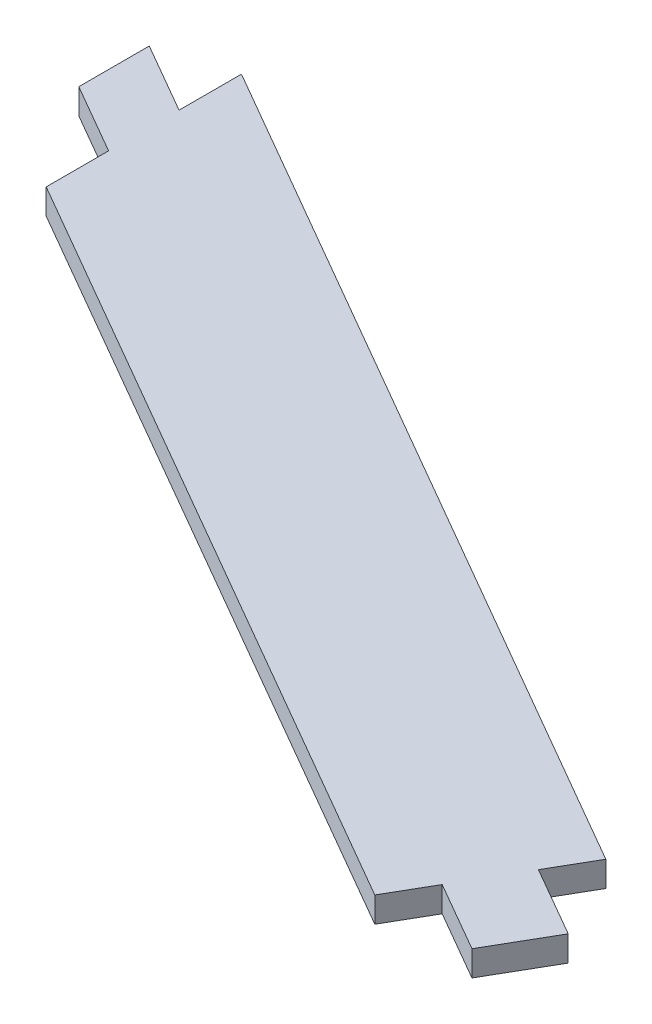
SolidWorks part; units mm, degrees
ref_plane "Front Plane" through (0, 0, 0) normal (0, 0, 1) x (1, 0, 0)
ref_plane "Top Plane" through (0, 0, 0) normal (0, 1, 0) x (1, 0, 0)
ref_plane "Right Plane" through (0, 0, 0) normal (1, 0, 0) x (0, 0, -1)
sketch "Sketch1" plane through (0, 0, 0) normal (0, 1, 0) x (1, 0, 0)
  line L0 (-363.1089, 480) -> (-363.1089, -480)
  line L1 (-363.1089, -480) -> (-303.1089, -480)
  line L2 (-303.1089, -480) -> (-303.1089, -400)
  line L3 (-303.1089, -400) -> (303.1089, -50)
  line L4 (303.1089, -50) -> (1036.8911, -50)
  line L5 (1036.8911, -50) -> (1036.8911, 50) construction
  line L6 (1036.8911, 50) -> (303.1089, 50)
  line L7 (303.1089, 50) -> (-303.1089, 400)
  line L8 (-303.1089, 400) -> (-303.1089, 480)
  line L9 (-303.1089, 480) -> (-363.1089, 480)
  line L10 (-363.1089, 0) -> (1036.8911, 0) construction
  line L11 (0, 225) -> (0, -225) construction
  line L14 (1036.8911, 50) -> (1066.8911, 50)
  line L15 (1036.8911, 50) -> (1036.8911, -50) construction
  line L16 (1036.8911, -50) -> (1066.8911, -50)
  line L17 (1066.8911, 50) -> (1066.8911, -50)
  dimension "D1" = 960
  dimension "D2" = 60
  dimension "D3" = 100
  dimension "D4" = 1400
  dimension "D5" = 150
  dimension "D6" = 80
  dimension "D7" = 30
extrude "Boss-Extrude1" add sketch "Sketch1" along normal blind 9
sketch "Sketch2" plane through (0, 9, 0) normal (0, 1, 0) x (1, 0, 0)
  line L1 (-363.1089, 480) -> (-303.1089, 480)
  line L2 (-363.1089, 480) -> (-363.1089, 400)
  line L3 (-363.1089, 400) -> (-303.1089, 400)
  line L4 (-303.1089, 480) -> (-303.1089, 400)
  line L5 (-363.1089, -480) -> (-303.1089, -480)
  line L6 (-363.1089, -480) -> (-363.1089, -400)
  line L7 (-363.1089, -400) -> (-303.1089, -400)
  line L8 (-303.1089, -480) -> (-303.1089, -400)
extrude "Boss-Extrude2" add sketch "Sketch2" along normal blind 500
sketch "Sketch3" plane through (0, 0, 0) normal (0, 0, 1) x (1, 0, 0)
  line L0 (-333.1089, 509) -> (-333.1089, 254.2) construction
  line L1 (-363.1089, 509) -> (-303.1089, 509) construction
  line L2 (-333.1089, 254.2) -> (-333.1089, 25) construction
  line L3 (-333.1089, 25) -> (-333.1089, 0) construction
  line L4 (-363.1089, 0) -> (-303.1089, 0) construction
  line L6 (-363.1089, 509) -> (-303.1089, 509)
  line L7 (-363.1089, 509) -> (-363.1089, 9)
  line L8 (-363.1089, 9) -> (-303.1089, 9)
  line L9 (-303.1089, 509) -> (-303.1089, 9)
  circle A0 centre (-333.1089, 254.2) radius 229.2
  circle A1 centre (-333.1089, 254.2) radius 6
  circle A2 centre (-333.1089, 254.2) radius 30
  dimension "D1" = 458.4
  dimension "D3" = 12
  dimension "D2" = 25
extrude "Cut-Extrude1" cut sketch "Sketch3" against normal through all both and the other way through all contours A2 L9 A0 L7 | A0 L9 L6 L7 | A1 region at (-333.1089, 495.8654, 0) region at (-333.1089, 380.1444, 0) region at (-333.1089, 254.2, 0)
sketch "Sketch4" plane through (0, 9, 0) normal (0, 1, 0) x (1, 0, 0)
  line L0 (866.8911, 25) -> (1066.8911, 25)
  line L2 (866.8911, -25) -> (1066.8911, -25)
  line L3 (1066.8911, -25) -> (1066.8911, 25)
  line L4 (866.8911, 0) -> (1066.8911, 0) construction
  line L5 (1066.8911, -50) -> (1066.8911, 50) construction
  circle A0 centre (866.8911, 0) radius 25
  dimension "D1" = 50
  dimension "D2" = 200
extrude "Cut-Extrude2" cut sketch "Sketch4" against normal through all contours L4 A0 L2 | A0 L4 L3 L0 | A0 region at (976.6223, 9, -12.7057) region at (884.0688, 9, -17.1777) region at (976.6223, 9, 12.7057)
sketch "Sketch16" plane through (0, 0, 0) normal (0, 0, 1) x (1, 0, 0)
  line L0 (-359.656, 240.2268) -> (-348.1089, 218.2888)
  line L5 (-348.1089, 218.2888) -> (-348.1089, 24)
  line L7 (-363.1089, 9) -> (-288.1089, 9)
  line L8 (303.1089, 9) -> (-303.1089, 9) construction
  line L9 (-303.1089, 254.2) -> (-303.1089, 24)
  line L10 (-348.1089, 24) -> (-363.1089, 9)
  line L11 (-303.1089, 254.2) -> (-303.1089, 9) construction
  line L12 (-303.1089, 24) -> (-288.1089, 9)
  line L13 (-348.1089, 24) -> (-303.1089, 24) construction
  line L14 (-346.3825, 247.2134) -> (-358.4836, 270.2039)
  line L15 (-319.8353, 261.1866) -> (-331.9364, 284.1771)
  circle A0 centre (-333.1089, 254.2) radius 15
  circle A1 centre (-333.1089, 254.2) radius 30
  arc A2 (-303.1089, 254.2) -> (-363.1089, 254.2) centre (-333.1089, 254.2) ccw construction
  circle A3 centre (-360.6089, 215.2) radius 12.5 construction
  dimension "D1" = 30
  dimension "D4" = 25
  dimension "D2" = 45
  dimension "D3" = 45
extrude "Boss-Extrude8" add sketch "Sketch16" along normal blind 305 and the other way blind 305 contours A1 L0 L5 L10 L7 L12 L9 | A1 L15 A0 L14 region at (-325.4564, 117.1914, 0) region at (-362.2383, 255.3393, 0)
sketch "Sketch17" plane through (0, 0, 0) normal (1, 0, 0) x (0, 0, -1)
  line L1 (230, 309) -> (-230, 309)
  line L2 (230, 309) -> (230, 9)
  line L3 (230, 9) -> (-230, 9)
  line L4 (-230, 309) -> (-230, 9)
  line L5 (0, 0) -> (0, 309) construction
  line L6 (480, 0) -> (-480, 0) construction
  dimension "D1" = 460
  dimension "D2" = 9
  dimension "D3" = 300
extrude "Cut-Extrude9" cut sketch "Sketch17" against normal through all
sketch "Sketch7" plane through (0, 0, 0) normal (1, 0, 0) x (0, 0, -1)
  line L1 (480, 284.2) -> (230, 284.2)
  line L2 (480, 284.2) -> (480, 9)
  line L3 (480, 9) -> (230, 9)
  line L4 (230, 284.2) -> (230, 9)
  line L5 (230, 218.2888) -> (230, 24) construction
  line L6 (471, 146.6) -> (444.5, 146.6) construction
  line L7 (480, 284.2) -> (471, 284.2)
  line L8 (480, 284.2) -> (480, 9)
  line L9 (480, 9) -> (471, 9)
  line L10 (471, 284.2) -> (471, 9)
  line L11 (400, 9) -> (409, 9)
  line L12 (400, 9) -> (400, 284.2)
  line L13 (400, 284.2) -> (409, 284.2)
  line L14 (409, 9) -> (409, 284.2)
  line L15 (444.5, 284.2) -> (435.5, 284.2)
  line L16 (444.5, 284.2) -> (444.5, 9)
  line L17 (444.5, 9) -> (435.5, 9)
  line L18 (435.5, 284.2) -> (435.5, 9)
  line L19 (444.5, 146.6) -> (435.5, 146.6) construction
  line L20 (435.5, 146.6) -> (409, 146.6) construction
  line L22 (0, 274.5241) -> (0, -136.9768) construction
  line L23 (-435.5, 146.6) -> (-409, 146.6) construction
  line L24 (305, 284.2) -> (296, 284.2)
  line L25 (305, 284.2) -> (305, 9)
  line L26 (305, 9) -> (296, 9)
  line L27 (296, 284.2) -> (296, 9)
  line L28 (239, 9) -> (230, 9)
  line L29 (239, 9) -> (239, 284.2)
  line L30 (239, 284.2) -> (230, 284.2)
  line L31 (230, 9) -> (230, 284.2)
  line L32 (-444.5, 146.6) -> (-435.5, 146.6) construction
  line L33 (-471, 146.6) -> (-444.5, 146.6) construction
  line L34 (-230, 9) -> (-230, 284.2)
  line L35 (-239, 284.2) -> (-230, 284.2)
  line L36 (-239, 9) -> (-239, 284.2)
  line L37 (-239, 9) -> (-230, 9)
  line L38 (-296, 284.2) -> (-296, 9)
  line L39 (-305, 9) -> (-296, 9)
  line L40 (-305, 284.2) -> (-305, 9)
  line L41 (-305, 284.2) -> (-296, 284.2)
  line L42 (-435.5, 284.2) -> (-435.5, 9)
  line L43 (-444.5, 9) -> (-435.5, 9)
  line L44 (-444.5, 284.2) -> (-444.5, 9)
  line L45 (-444.5, 284.2) -> (-435.5, 284.2)
  line L46 (-409, 9) -> (-409, 284.2)
  line L47 (-400, 284.2) -> (-409, 284.2)
  line L48 (-400, 9) -> (-400, 284.2)
  line L49 (-400, 9) -> (-409, 9)
  line L50 (-471, 284.2) -> (-471, 9)
  line L51 (-480, 9) -> (-471, 9)
  line L52 (-480, 284.2) -> (-480, 9)
  line L53 (-480, 284.2) -> (-471, 284.2)
  line L54 (-230, 284.2) -> (-230, 9)
  line L55 (-480, 9) -> (-230, 9)
  line L56 (-480, 284.2) -> (-480, 9)
  line L57 (-480, 284.2) -> (-230, 284.2)
  line L58 (305, 218.2888) -> (305, 24) construction
  dimension "D1" = 9
  dimension "D2" = 9
  dimension "D3" = 9
  dimension "D4" = 9
  dimension "D5" = 9
extrude "Cut-Extrude4" cut sketch "Sketch7" against normal through all both and the other way through all contours L1 L16 L3 L10 | L18 L1 L14 L3 | L29 L3 L27 L1 | L57 L38 L55 L36 | L57 L42 L55 L46 | L57 L50 L55 L44 | L1 L18 L3 L16 | L45 L44 L43 L42 region at (0, 146.6, -457.75) region at (0, 146.6, -440) region at (0, 146.6, -422.25) region at (0, 146.6, -267.5) region at (0, 146.6, 267.5) region at (0, 146.6, 422.25) region at (0, 146.6, 440) region at (0, 146.6, 457.75)
sketch "Sketch10" plane through (0, 9, 0) normal (0, 1, 0) x (1, 0, 0)
  line L0 (-363.1089, 221) -> (-113.0718, 221)
  line L2 (-113.0718, 221) -> (269.7114, 0)
  line L3 (269.7114, 0) -> (-113.0718, -221)
  line L4 (-113.0718, -221) -> (-363.1089, -221)
  line L5 (-363.1089, -221) -> (-363.1089, 221)
  line L6 (0, 0) -> (269.7114, 0) construction
  line L7 (-363.1089, 0) -> (0, 0) construction
  line L8 (-113.0718, -221) -> (-113.0718, 221) construction
  line L9 (303.1089, 50) -> (-303.1089, 400) construction
  line L10 (-363.1089, -230) -> (-363.1089, 230) construction
  line L11 (303.1089, 50) -> (337.7499, 30)
  line L12 (337.7499, 30) -> (806.8911, 30)
  line L13 (806.8911, 30) -> (841.5321, 50)
  line L14 (1066.8911, 50) -> (303.1089, 50) construction
  line L15 (841.5321, 50) -> (303.1089, 50)
  line L16 (303.1089, -50) -> (337.7499, -30)
  line L17 (337.7499, -30) -> (806.8911, -30)
  line L18 (806.8911, -30) -> (841.5321, -50)
  line L19 (303.1089, -50) -> (1066.8911, -50) construction
  line L20 (841.5321, -50) -> (303.1089, -50)
  line L21 (337.7499, -30) -> (337.7499, 30) construction
  line L22 (269.7114, 0) -> (337.7499, 0) construction
  line L23 (806.8911, 30) -> (806.8911, -30) construction
  line L24 (-303.1089, -400) -> (303.1089, -50) construction
  line L25 (841.5321, 50) -> (841.5321, -50) construction
  line L27 (-363.1089, 230) -> (-288.1089, 230) construction
  line L28 (-363.1089, -230) -> (-288.1089, -230) construction
  arc A0 (866.8911, 25) -> (866.8911, -25) centre (866.8911, 0) ccw construction
  dimension "D1" = 60
  dimension "D2" = 30
  dimension "D3" = 60
  dimension "D4" = 60
  dimension "D5" = 9
  dimension "D6" = 9
extrude "Cut-Extrude6" cut sketch "Sketch10" against normal through all
sketch "Sketch11" plane through (-363.1089, 0, 0) normal (-1, 0, 0) x (0, 0, 1)
  line L0 (-480, 254.2) -> (-480, 0) construction
  line L1 (-480, 224.2) -> (-400, 224.2)
  line L2 (-480, 224.2) -> (-480, 215.2)
  line L3 (-480, 215.2) -> (-400, 215.2)
  line L4 (-400, 224.2) -> (-400, 215.2)
  line L5 (-400, 254.2) -> (-400, 9) construction
  line L6 (400, 254.2) -> (400, 9) construction
  line L7 (400, 224.2) -> (480, 224.2)
  line L8 (400, 224.2) -> (400, 215.2)
  line L9 (400, 215.2) -> (480, 215.2)
  line L10 (480, 224.2) -> (480, 215.2)
  line L11 (480, 254.2) -> (480, 0) construction
  line L12 (-400, 224.2) -> (400, 224.2) construction
  line L13 (400, 215.2) -> (-400, 215.2) construction
  line L14 (-400, 284.2) -> (-409, 284.2) construction
  dimension "D1" = 9
  dimension "D2" = 60
extrude "Boss-Extrude5" add sketch "Sketch11" against normal up to surface (60 mm away) up to face at (-303.1089, 115.9778, 435.5556)
sketch "Sketch18" plane through (-348.1089, 0, 0) normal (-1, 0, 0) x (0, 0, 1)
  line L0 (-230, 218.2888) -> (-230, 24) construction
  line L1 (-305, 218.2888) -> (-230, 218.2888)
  line L2 (-305, 218.2888) -> (-305, 209.2888)
  line L3 (-305, 209.2888) -> (-230, 209.2888)
  line L4 (-230, 218.2888) -> (-230, 209.2888)
  line L5 (230, 24) -> (230, 218.2888) construction
  line L6 (305, 218.2888) -> (230, 218.2888)
  line L7 (305, 218.2888) -> (305, 209.2888)
  line L8 (305, 209.2888) -> (230, 209.2888)
  line L9 (230, 218.2888) -> (230, 209.2888)
  dimension "D1" = 9
  dimension "D2" = 9
extrude "Boss-Extrude9" add sketch "Sketch18" against normal up to surface (45 mm away) up to face at (-303.1089, 139.1, -234.5)
sketch "Sketch12" plane through (0, 9, 0) normal (0, 1, 0) x (1, 0, 0)
  line L0 (-363.1089, -480) -> (-303.1089, -480) construction
  line L1 (-363.1089, 480) -> (-303.1089, 480)
  line L2 (-363.1089, 480) -> (-363.1089, 489)
  line L3 (-363.1089, 489) -> (-303.1089, 489)
  line L4 (-303.1089, 480) -> (-303.1089, 489)
  line L5 (-363.1089, -480) -> (-303.1089, -480)
  line L6 (-363.1089, -480) -> (-363.1089, -489)
  line L7 (-363.1089, -489) -> (-303.1089, -489)
  line L8 (-303.1089, -480) -> (-303.1089, -489)
  dimension "D1" = 9
  dimension "D2" = 9
extrude "Boss-Extrude6" add sketch "Sketch12" against normal blind 9
fillet "Fillet3" radius 9 27 edges at (-303.1089, 4.5, -489) (-363.1089, 4.5, -489) (-363.1089, 4.5, -221) (-363.1089, 4.5, 221) (-363.1089, 4.5, 489) (-303.1089, 4.5, 489) (841.5321, 4.5, 50) (806.8911, 4.5, 30) (841.5321, 4.5, -50) (806.8911, 4.5, -30) (337.7499, 4.5, -30) (337.7499, 4.5, 30) (269.7114, 4.5, 0) (-113.0718, 4.5, 221) (-113.0718, 4.5, -221) (-303.1089, 24, -234.5) (-303.1089, 24, -300.5) (-303.1089, 24, 234.5) (-303.1089, 24, 300.5) (-348.1089, 24, 234.5) (-348.1089, 24, 300.5) (-348.1089, 24, -234.5) (-348.1089, 24, -300.5) (1066.8911, 4.5, 50) (1066.8911, 4.5, 25) (1066.8911, 4.5, -25) (1066.8911, 4.5, -50)
sketch "Sketch15" plane through (0, 9, 0) normal (0, 1, 0) x (1, 0, 0)
  line L0 (-83.154, 230) -> (-83.154, -230)
  line L1 (-113.154, 230) -> (-113.154, 220.6933) construction
  line L2 (-363.1089, 230) -> (-288.1089, 230) construction
  line L4 (-83.154, -230) -> (-143.154, -230)
  line L5 (-143.154, -230) -> (-143.154, 230)
  line L6 (-143.154, 230) -> (-83.154, 230)
  line L7 (0, 0) -> (-83.154, 0) construction
  arc A0 (-110.9833, 219.7942) -> (-115.4833, 221) centre (-115.4833, 212) ccw construction
  dimension "D1" = 60
extrude "Boss-Extrude7" add sketch "Sketch15" against normal blind 9
fillet "Fillet4" radius 9 4 edges at (-83.154, 4.5, -203.7269) (-83.154, 4.5, 203.7269) (-143.154, 4.5, 221) (-143.154, 4.5, -221)
sketch "Sketch20" plane through (0, 9, 0) normal (0, 1, 0) x (1, 0, 0)
  line L0 (-348.1089, 480) -> (-348.1089, 400)
  line L1 (-363.1089, 480) -> (-303.1089, 480)
  line L2 (-363.1089, 480) -> (-363.1089, 471)
  line L3 (-363.1089, 471) -> (-303.1089, 471)
  line L4 (-303.1089, 480) -> (-303.1089, 471)
  line L5 (-363.1089, 409) -> (-303.1089, 409)
  line L6 (-363.1089, 409) -> (-363.1089, 400)
  line L7 (-363.1089, 400) -> (-303.1089, 400)
  line L8 (-303.1089, 409) -> (-303.1089, 400)
  line L9 (-363.1089, 305) -> (-288.1089, 305)
  line L10 (-363.1089, 305) -> (-363.1089, 296)
  line L11 (-363.1089, 296) -> (-288.1089, 296)
  line L12 (-288.1089, 305) -> (-288.1089, 296)
  line L13 (-363.1089, 239) -> (-288.1089, 239)
  line L14 (-363.1089, 239) -> (-363.1089, 230)
  line L15 (-363.1089, 230) -> (-288.1089, 230)
  line L16 (-288.1089, 239) -> (-288.1089, 230)
  line L17 (-318.1089, 480) -> (-318.1089, 400)
  line L18 (-363.1089, 440) -> (-348.1089, 440) construction
  line L19 (-363.1089, 409) -> (-363.1089, 471) construction
  line L20 (-348.1089, 440) -> (-318.1089, 440) construction
  line L21 (-318.1089, 440) -> (-303.1089, 440) construction
  line L22 (-303.1089, 471) -> (-303.1089, 409) construction
  line L23 (-340.6089, 305) -> (-340.6089, 230)
  line L24 (-310.6089, 305) -> (-310.6089, 230)
  line L25 (-288.1089, 296) -> (-288.1089, 239) construction
  line L26 (-363.1089, 267.5) -> (-340.6089, 267.5) construction
  line L27 (-363.1089, 296) -> (-363.1089, 239) construction
  line L28 (-340.6089, 267.5) -> (-310.6089, 267.5) construction
  line L29 (-310.6089, 267.5) -> (-288.1089, 267.5) construction
  line L30 (-512.4702, 0) -> (462.9433, 0) construction
  line L31 (-310.6089, -267.5) -> (-288.1089, -267.5) construction
  line L32 (-340.6089, -267.5) -> (-310.6089, -267.5) construction
  line L33 (-363.1089, -267.5) -> (-340.6089, -267.5) construction
  line L34 (-288.1089, -296) -> (-288.1089, -239) construction
  line L35 (-318.1089, -440) -> (-303.1089, -440) construction
  line L36 (-348.1089, -440) -> (-318.1089, -440) construction
  line L37 (-363.1089, -440) -> (-348.1089, -440) construction
  line L38 (-310.6089, -305) -> (-310.6089, -230)
  line L39 (-340.6089, -305) -> (-340.6089, -230)
  line L40 (-318.1089, -480) -> (-318.1089, -400)
  line L41 (-288.1089, -239) -> (-288.1089, -230)
  line L42 (-363.1089, -230) -> (-288.1089, -230)
  line L43 (-363.1089, -239) -> (-363.1089, -230)
  line L44 (-363.1089, -239) -> (-288.1089, -239)
  line L45 (-288.1089, -305) -> (-288.1089, -296)
  line L46 (-363.1089, -296) -> (-288.1089, -296)
  line L47 (-363.1089, -305) -> (-363.1089, -296)
  line L48 (-363.1089, -305) -> (-288.1089, -305)
  line L49 (-303.1089, -409) -> (-303.1089, -400)
  line L50 (-363.1089, -400) -> (-303.1089, -400)
  line L51 (-363.1089, -409) -> (-363.1089, -400)
  line L52 (-363.1089, -409) -> (-303.1089, -409)
  line L53 (-303.1089, -480) -> (-303.1089, -471)
  line L54 (-363.1089, -471) -> (-303.1089, -471)
  line L55 (-363.1089, -480) -> (-363.1089, -471)
  line L56 (-363.1089, -480) -> (-303.1089, -480)
  line L57 (-348.1089, -480) -> (-348.1089, -400)
  dimension "D1" = 30
  dimension "D2" = 30
sketch "Sketch21" plane through (0, 9, 0) normal (0, 1, 0) x (1, 0, 0)
  line L0 (1066.8911, 34) -> (1066.8911, 41) construction
  line L1 (-363.1089, 489) -> (1066.8911, 489)
  line L2 (-363.1089, 489) -> (-363.1089, -489)
  line L3 (-363.1089, -489) -> (1066.8911, -489)
  line L4 (1066.8911, 489) -> (1066.8911, -489)
  line L5 (-354.1089, -489) -> (-312.1089, -489) construction
  line L6 (-363.1089, -305) -> (-363.1089, -400) construction
  line L7 (-312.1089, 489) -> (-354.1089, 489) construction
extrude "Cut-Extrude11" cut sketch "Sketch20" against normal through all both and the other way through all contours L56 L57 L54 L55 | L40 L56 L53 L54 | L52 L57 L50 L51 | L40 L52 L49 L50 | L47 L48 L39 L46 | L38 L48 L45 L46 | L38 L44 L41 L42 | L43 L44 L39 L42 | L23 L13 L14 L15 | L13 L24 L15 L16 | L9 L24 L11 L12 | L23 L9 L10 L11 | L6 L7 L0 L5 | L5 L17 L7 L8 | L1 L17 L3 L4 | L2 L3 L0 L1 region at (-355.6089, 9, -475.5) region at (-310.6089, 9, -475.5) region at (-355.6089, 9, -404.5) region at (-310.6089, 9, -404.5) region at (-351.8589, 9, -300.5) region at (-299.3589, 9, -300.5) region at (-351.8589, 9, -234.5) region at (-299.3589, 9, -234.5) region at (-299.3589, 9, 300.5) region at (-351.8589, 9, 300.5) region at (-299.3589, 9, 234.5) region at (-351.8589, 9, 234.5) region at (-310.6089, 9, 475.5) region at (-355.6089, 9, 475.5) region at (-310.6089, 9, 404.5) region at (-355.6089, 9, 404.5)
extrude "Cut-Extrude12" cut sketch "Sketch21" along normal through all
sketch "Sketch22" plane through (0, 9, 0) normal (0, 1, 0) x (1, 0, 0)
  line L0 (1066.8911, 34) -> (1066.8911, 41) construction
  line L1 (-363.1089, -489) -> (1066.8911, -489)
  line L2 (-363.1089, -489) -> (-363.1089, 489)
  line L3 (-363.1089, 489) -> (1066.8911, 489)
  line L4 (1066.8911, -489) -> (1066.8911, 489)
  line L5 (-312.1089, 489) -> (-354.1089, 489) construction
  line L6 (-363.1089, 471) -> (-363.1089, 409) construction
  line L7 (-354.1089, -489) -> (-312.1089, -489) construction
  line L8 (-83.154, 188.1385) -> (-143.154, 188.1385)
  line L9 (-143.154, 212) -> (-143.154, -212) construction
  line L10 (-113.154, 188.1385) -> (-113.154, 213.1385) construction
  line L11 (-69.654, 195.9327) -> (-69.654, 265.2147)
  line L12 (-125.654, 188.1385) -> (-100.654, 188.1385)
  line L13 (256.2114, 7.7942) -> (286.2114, 59.7558)
  line L14 (256.2114, 7.7942) -> (231.2114, 22.228)
  line L15 (231.2114, 22.228) -> (239.9614, 37.3834)
  line L16 (335.6615, 31.2058) -> (-303.1089, 400) construction
  line L17 (256.2114, 7.7942) -> (256.2114, -7.7942)
  line L18 (-69.654, 265.2147) -> (-297.5196, 489)
  line L19 (-143.154, 188.1385) -> (-363.1089, 188.1385)
  line L20 (340.1615, 88.1184) -> (-69.654, 265.2147)
  line L21 (340.1615, 88.1184) -> (1066.8911, 88.1184)
  line L22 (194.4241, 7.7942) -> (-83.154, 188.1385)
  line L23 (-69.654, 195.9327) -> (-83.154, 188.1385)
  line L24 (-125.654, 188.1385) -> (-125.654, 213.1385)
  line L25 (-125.654, 213.1385) -> (-100.654, 213.1385)
  line L26 (-100.654, 188.1385) -> (-100.654, 213.1385)
  line L27 (-69.654, 195.9327) -> (-44.654, 181.4989)
  line L28 (256.2114, 7.7942) -> (-69.654, 195.9327) construction
  line L29 (-44.654, 181.4989) -> (-44.654, 203.64)
  line L30 (-44.654, 203.64) -> (-69.654, 218.0737)
  line L32 (-69.654, 265.2147) -> (-44.654, 250.781)
  line L33 (-44.654, 250.781) -> (-44.654, 228.64)
  line L34 (-44.654, 228.64) -> (-69.654, 243.0737)
  line L35 (-44.654, 203.64) -> (-44.654, 228.64)
  line L36 (239.9614, 37.3834) -> (264.9614, 22.9497)
  line L37 (239.9614, 37.3834) -> (252.4614, 59.0341)
  line L38 (252.4614, 59.0341) -> (277.4614, 44.6003)
  line L39 (252.4614, 59.0341) -> (261.2114, 74.1895)
  line L40 (261.2114, 74.1895) -> (286.2114, 59.7558)
  line L41 (194.4241, 7.7942) -> (256.2114, 7.7942)
  line L42 (286.2114, 59.7558) -> (340.1615, 88.1184)
  line L43 (-181.378, 0) -> (-33.8367, 0) construction
  line L44 (-113.154, -188.1385) -> (-113.154, -213.1385) construction
  line L45 (286.2114, -59.7558) -> (340.1615, -88.1184)
  line L46 (194.4241, -7.7942) -> (256.2114, -7.7942)
  line L47 (261.2114, -74.1895) -> (286.2114, -59.7558)
  line L48 (252.4614, -59.0341) -> (261.2114, -74.1895)
  line L49 (252.4614, -59.0341) -> (277.4614, -44.6003)
  line L50 (239.9614, -37.3834) -> (252.4614, -59.0341)
  line L51 (239.9614, -37.3834) -> (264.9614, -22.9497)
  line L52 (-44.654, -203.64) -> (-44.654, -228.64)
  line L53 (-44.654, -228.64) -> (-69.654, -243.0737)
  line L54 (-44.654, -250.781) -> (-44.654, -228.64)
  line L55 (-69.654, -265.2147) -> (-44.654, -250.781)
  line L56 (-44.654, -203.64) -> (-69.654, -218.0737)
  line L57 (-44.654, -181.4989) -> (-44.654, -203.64)
  line L58 (-69.654, -195.9327) -> (-44.654, -181.4989)
  line L59 (-100.654, -188.1385) -> (-100.654, -213.1385)
  line L60 (-125.654, -213.1385) -> (-100.654, -213.1385)
  line L61 (-125.654, -188.1385) -> (-125.654, -213.1385)
  line L62 (-69.654, -195.9327) -> (-83.154, -188.1385)
  line L63 (194.4241, -7.7942) -> (-83.154, -188.1385)
  line L64 (340.1615, -88.1184) -> (1066.8911, -88.1184)
  line L65 (340.1615, -88.1184) -> (-69.654, -265.2147)
  line L66 (-143.154, -188.1385) -> (-363.1089, -188.1385)
  line L67 (-69.654, -265.2147) -> (-297.5196, -489)
  line L68 (231.2114, -22.228) -> (239.9614, -37.3834)
  line L69 (256.2114, -7.7942) -> (231.2114, -22.228)
  line L70 (256.2114, -7.7942) -> (286.2114, -59.7558)
  line L71 (-125.654, -188.1385) -> (-100.654, -188.1385)
  line L72 (-69.654, -195.9327) -> (-69.654, -265.2147)
  line L73 (-83.154, -188.1385) -> (-143.154, -188.1385)
  line L74 (-363.1089, -489) -> (1066.8911, -489)
  line L75 (194.4241, -7.7942) -> (194.4241, 7.7942)
  dimension "D1" = 25
  dimension "D2" = 25
  dimension "D3" = 25
  dimension "D4" = 25
  dimension "D5" = 25
  dimension "D6" = 25
extrude "Cut-Extrude13" cut sketch "Sketch22" against normal through all contours L26 L8 L23 L11 L18 L3 L2 L19 L24 L25 | L34 L33 L32 L11 | L29 L30 L11 L27 | L17 L70 L45 L64 L4 L21 L42 L13 | L36 L15 L14 L13 | L40 L39 L38 L13 region at (-246.5905, 9, -308.954) region at (674.7852, 9, 0) region at (-57.154, 9, -246.9274) region at (269.3364, 9, -59.3949) region at (-57.154, 9, -199.7863) region at (248.0864, 9, -22.5888)
